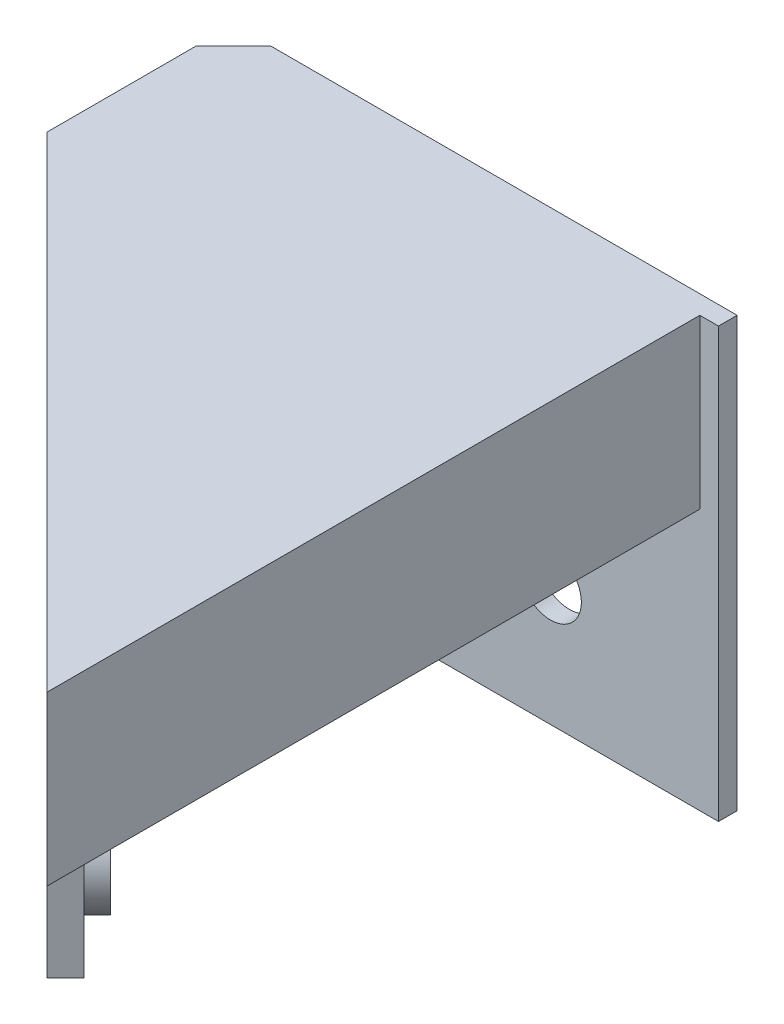
SolidWorks part; units mm, degrees
ref_plane "Front Plane" through (0, 0, 0) normal (0, 0, 1) x (1, 0, 0)
ref_plane "Top Plane" through (0, 0, 0) normal (0, 1, 0) x (1, 0, 0)
ref_plane "Right Plane" through (0, 0, 0) normal (1, 0, 0) x (0, 0, -1)
sketch "Sketch1" plane through (0, 0, 0) normal (0, 0, 1) x (1, 0, 0)
  line L1 (8.2499, -29.45) -> (-16.7501, -29.45)
  line L2 (8.2499, -29.45) -> (8.2499, -6.45)
  line L3 (8.2499, -6.45) -> (-16.7501, -6.45)
  line L4 (-16.7501, -29.45) -> (-16.7501, -6.45)
  point P0 (0, 0)
  point P9 (0, 0)
  dimension "D2" = 25
  dimension "D1" = 23
extrude "Boss-Extrude1" add sketch "Sketch1" along normal blind 1 contours L4 L1 L2 L3 region at (-4.2501, -17.95, 0)
sketch "Sketch4" plane through (-16.7501, 0, 0) normal (-1, 0, 0) x (0, 0, 1)
  line L0 (1, -29.45) -> (0, -29.45) construction
  line L1 (0, -6.45) -> (10, -6.45)
  line L2 (0, -6.45) -> (0, -29.45)
  line L3 (0, -29.45) -> (10, -29.45)
  line L4 (10, -6.45) -> (10, -29.45)
  dimension "D1" = 10
extrude "Boss-Extrude3" add sketch "Sketch4" along normal blind 2
sketch "Sketch5" plane through (0, -29.45, 0) normal (0, -1, 0) x (1, 0, 0)
  line L0 (-18.7501, 10) -> (-2.4866, 26.2635)
  line L1 (-2.4866, 26.2635) -> (-1.4866, 25.2635)
  line L2 (-1.4866, 25.2635) -> (-16.7501, 10)
  line L3 (-16.7501, 1) -> (-16.7501, 10) construction
  line L4 (-16.7501, 10) -> (-18.7501, 10)
  dimension "D1" = 135
  dimension "D2" = 23
extrude "Boss-Extrude4" add sketch "Sketch5" against normal up to surface (23 mm away) up to face at (-9.0834, -6.45, 3.6667)
sketch "Sketch6" plane through (-13.375, 0, 13.375) normal (0.7071, 0, -0.7071) x (-0.7071, 0, -0.7071)
  line L0 (-16.8128, -6.45) -> (-16.8128, -29.45) construction
  line L2 (4.773, -29.45) -> (-16.8128, -29.45) construction
  line L3 (-11.8128, -26.45) -> (-11.8128, -18.45) construction
  circle A1 centre (-11.8128, -26.45) radius 1.65
  circle A2 centre (-11.8128, -18.45) radius 1.65
  dimension "D1" = 8
  dimension "D4" = 5
  dimension "D5" = 3
  dimension "D6" = 3.3
extrude "Cut-Extrude1" cut sketch "Sketch6" against normal blind 2
chamfer "Chamfer1" distance 1 angle 45 1 edges at (-16.7501, -17.95, 1)
sketch "Sketch7" plane through (0, 0, 1) normal (0, 0, 1) x (1, 0, 0)
  line L0 (-18.7501, -6.45) -> (-2.4866, -6.45) construction
  line L1 (-14.7501, -14.45) -> (6.2499, -14.45)
  line L2 (-14.7501, -14.45) -> (-14.7501, -7.45)
  line L3 (-14.7501, -7.45) -> (6.2499, -7.45)
  line L4 (6.2499, -14.45) -> (6.2499, -7.45)
  line L5 (-14.7501, -14.45) -> (6.2499, -7.45) construction
  line L6 (-14.7501, -7.45) -> (6.2499, -14.45) construction
  line L14 (8.2499, -29.45) -> (8.2499, -6.45) construction
  line L15 (-18.7501, -6.45) -> (-18.7501, -29.45) construction
  point P0 (-4.2501, -10.95)
  point P5 (-4.2501, -10.95)
  dimension "D1" = 4
  dimension "D2" = 7
  dimension "D3" = 1
  dimension "D4" = 2
extrude "Cut-Extrude3" cut sketch "Sketch7" against normal up to surface (1 mm away) and the other way up to surface up to face at (-5.2501, -17.95, 0) other way up to face at (-4.8554, -18.45, 23.8946)
sketch "Sketch9" plane through (0, 0, 0) normal (0, 0, -1) x (-1, 0, 0)
  line L0 (-8.2499, -17.95) -> (18.7501, -17.95) construction
  line L1 (-7.2499, -15.45) -> (18.7501, -15.45)
  line L2 (-7.2499, -15.45) -> (-7.2499, -6.45)
  line L3 (-7.2499, -6.45) -> (18.7501, -6.45)
  line L4 (18.7501, -15.45) -> (18.7501, -6.45)
  line L5 (-8.2499, -29.45) -> (-8.2499, -6.45) construction
  line L6 (-6.2499, -14.45) -> (14.7501, -14.45) construction
  line L9 (14.7501, -7.45) -> (-6.2499, -7.45) construction
  line L10 (-6.2499, -7.45) -> (-6.2499, -14.45) construction
  line L11 (-6.2499, -14.45) -> (14.7501, -14.45)
  line L12 (-6.2499, -14.45) -> (-6.2499, -7.45)
  line L13 (-6.2499, -7.45) -> (14.7501, -7.45)
  line L14 (14.7501, -14.45) -> (14.7501, -7.45)
  line L15 (-6.2499, -14.45) -> (14.7501, -7.45) construction
  line L16 (-6.2499, -7.45) -> (14.7501, -14.45) construction
  line L17 (18.7501, -6.45) -> (18.7501, -29.45) construction
  point P0 (12.425, 0)
  point P13 (4.2501, -10.95)
  dimension "D1" = 1
  dimension "D2" = 1
  dimension "D4" = 1
extrude "Boss-Extrude6" add sketch "Sketch9" against normal up to surface (36 mm away) up to face at (-9.6183, -14.45, 19.1317)
chamfer "Chamfer3" distance 2 angle 45 1 edges at (-18.7501, -17.95, 0)
sketch "Sketch10" plane through (0, 0, 1) normal (0, 0, 1) x (1, 0, 0)
  line L0 (8.2499, -29.45) -> (-15.7501, -29.45) construction
  line L1 (8.2499, -29.45) -> (8.2499, -6.45) construction
  circle A0 centre (-0.7501, -22.95) radius 1.65
  dimension "D1" = 6.5
  dimension "D2" = 9
  dimension "D3" = 3.3
extrude "Cut-Extrude4" cut sketch "Sketch10" against normal blind 10
sketch "Sketch11" plane through (0, 0, 0) normal (0, 0, -1) x (-1, 0, 0)
  line L0 (-6.2499, -14.45) -> (14.7501, -14.45) construction
  line L1 (-5.1499, -14.45) -> (-2.3499, -14.45)
  line L2 (-5.1499, -14.45) -> (-5.1499, -17.35)
  line L3 (-5.1499, -17.35) -> (-2.3499, -17.35)
  line L4 (-2.3499, -14.45) -> (-2.3499, -17.35)
  line L5 (-8.2499, -29.45) -> (-8.2499, -6.45) construction
  line L6 (10.8501, -14.45) -> (13.6501, -14.45)
  line L7 (10.8501, -14.45) -> (10.8501, -17.35)
  line L8 (10.8501, -17.35) -> (13.6501, -17.35)
  line L9 (13.6501, -14.45) -> (13.6501, -17.35)
  line L10 (16.7501, -29.45) -> (16.7501, -6.45) construction
  dimension "D1" = 2.8
  dimension "D2" = 2.9
  dimension "D3" = 3.1
  dimension "D4" = 3.1
  dimension "D5" = 2.8
  dimension "D6" = 2.9
extrude "Boss-Extrude7" add sketch "Sketch11" along normal blind 3
sketch "Sketch12" plane through (-13.375, 0, 13.375) normal (0.7071, 0, -0.7071) x (-0.7071, 0, -0.7071)
  circle A0 centre (-11.8128, -18.45) radius 2.95
  circle A1 centre (-11.8128, -18.45) radius 1.65
  circle A2 centre (-11.8128, -26.45) radius 1.65
  circle A3 centre (-11.8128, -26.45) radius 2.95
  dimension "D1" = 1.3
  dimension "D2" = 1.3
extrude "Boss-Extrude8" add sketch "Sketch12" along normal blind 1
